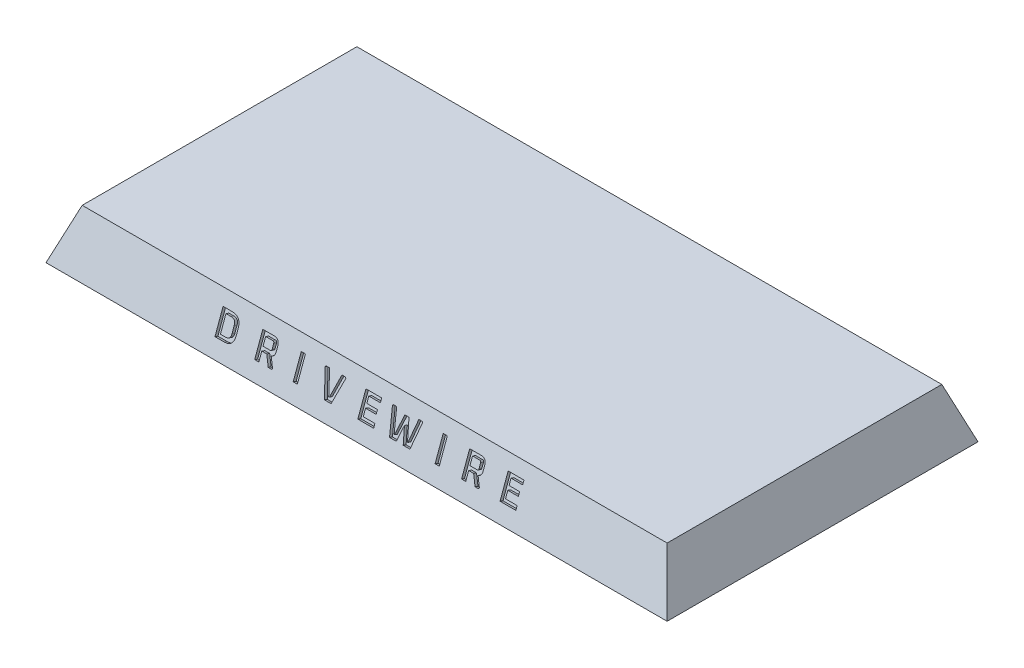
SolidWorks part; units mm, degrees
ref_plane "Front Plane" through (0, 0, 0) normal (0, 0, 1) x (1, 0, 0)
ref_plane "Top Plane" through (0, 0, 0) normal (0, 1, 0) x (1, 0, 0)
ref_plane "Right Plane" through (0, 0, 0) normal (1, 0, 0) x (0, 0, -1)
sketch "Sketch1" plane through (0, 0, 0) normal (0, 1, 0) x (1, 0, 0)
  line L1 (-100, -15) -> (100, -15)
  line L2 (-100, -15) -> (-100, 15)
  line L3 (-100, 15) -> (100, 15)
  line L4 (100, -15) -> (100, 15)
  line L5 (-100, -15) -> (100, 15) construction
  line L6 (-100, 15) -> (100, -15) construction
  point P0 (0, 0)
  point P6 (0, 0)
  dimension "D1" = 30
  dimension "D2" = 200
extrude "Boss-Extrude1" add sketch "Sketch1" along normal blind 16 draft 20
sketch "Sketch2" plane through (0, 0, 0) normal (0, 1, 0) x (1, 0, 0)
  point P0 (0, 0)
sketch "Sketch4" plane through (0, 4.8209, 13.2453) normal (0, 0.342, 0.9397) x (1, 0, 0)
  text T0 "D  R  I  V  E W  I  R  E" font "Oxanium SemiBold" height in points 28
  point P1 (0, 0)
  point P2 (-53.7077, -3.6249)
  point P3 (0, 0)
  point P4 (-60.1948, 0)
  point P5 (-42.6946, -1.5128)
  point P6 (-50.8412, 1.2028)
  point P7 (-48.2765, 0)
extrude "Cut-Extrude2" cut sketch "Sketch4" against normal blind 1
sketch "Sketch11" plane through (0, 4.8209, -13.2453) normal (0, 0.342, -0.9397) x (-1, 0, 0)
  line L0 (-94.1765, 11.8965) -> (94.1765, 11.8965)
  line L1 (94.1765, 11.8965) -> (100, -5.1303)
  line L2 (100, -5.1303) -> (-100, -5.1303)
  line L3 (-100, -5.1303) -> (-94.1765, 11.8965)
extrude "Boss-Extrude2" add sketch "Sketch11" along direction (0, 0, 1) on the side of the normal blind 35.05
move or copy body "Body-Move/Copy1" bodies to move or copy 108 copy no translate (0, 0, 35.05) parameters "D1"=0, "D2"=0, "D3"=35.05
extrude "Boss-Extrude3" add sketch "Sketch11<2>" along direction (0, 0, -1) on the side of the normal blind 35.05
sketch "Sketch11<2>" plane through (0, 4.8209, -13.2453) normal (0, 0.342, -0.9397) x (-1, 0, 0) same geometry as "Sketch11"
